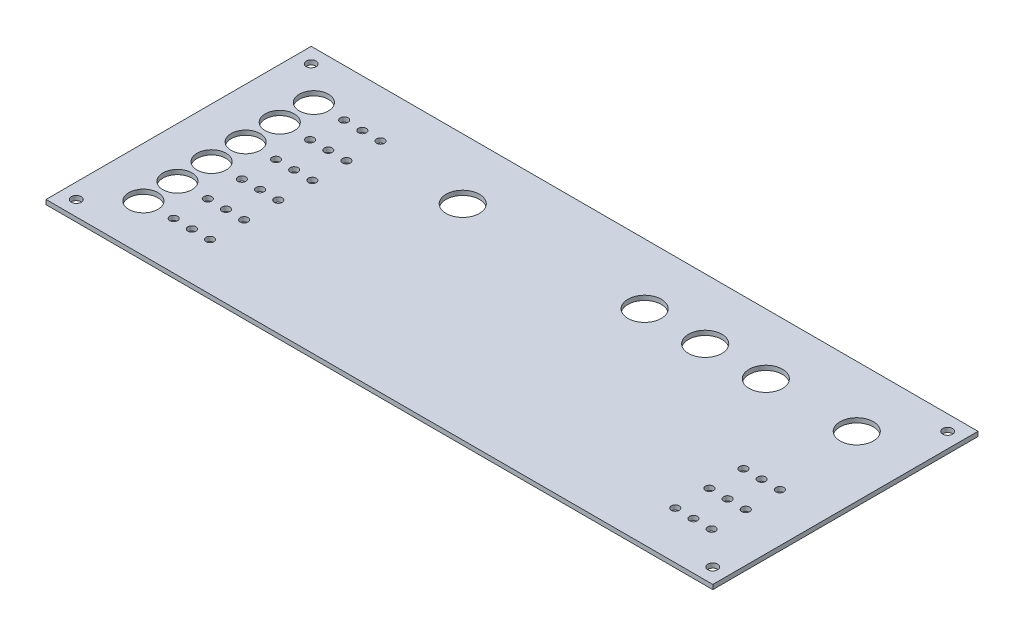
SolidWorks part; units mm, degrees
ref_plane "Front Plane" through (0, 0, 0) normal (0, 0, 1) x (1, 0, 0)
ref_plane "Top Plane" through (0, 0, 0) normal (0, 1, 0) x (1, 0, 0)
ref_plane "Right Plane" through (0, 0, 0) normal (1, 0, 0) x (0, 0, -1)
sketch "Sketch1" plane through (0, 0, 0) normal (0, 1, 0) x (1, 0, 0)
  line L0 (420, 20) -> (20, 20) construction
  line L1 (440, 175) -> (0, 175)
  line L2 (440, 175) -> (440, 0)
  line L3 (440, 0) -> (0, 0)
  line L4 (0, 175) -> (0, 0)
  line L5 (20, 155) -> (20, 20) construction
  line L6 (420, 155) -> (20, 155) construction
  line L7 (420, 155) -> (420, 20) construction
  line L9 (20, 143.75) -> (120, 143.75) construction
  line L10 (33, 20) -> (33, 155) construction
  line L11 (20, 121.25) -> (120, 121.25) construction
  line L12 (53, 20) -> (53, 155) construction
  line L13 (120, 98.75) -> (20, 98.75) construction
  line L14 (65, 20) -> (65, 155) construction
  line L15 (20, 76.25) -> (420, 76.25) construction
  line L16 (77, 20) -> (77, 155) construction
  line L17 (420, 53.75) -> (20, 53.75) construction
  line L19 (20, 31.25) -> (420, 31.25) construction
  line L20 (420, 135) -> (140, 135) construction
  circle A0 centre (10, 10) radius 3.25
  circle A1 centre (10, 165) radius 3.25
  circle A2 centre (430, 165) radius 3.25
  circle A3 centre (430, 10) radius 3.25
  circle A4 centre (33, 31.25) radius 9.6
  circle A5 centre (33, 53.75) radius 9.6
  circle A6 centre (33, 76.25) radius 9.6
  circle A7 centre (33, 98.75) radius 9.6
  circle A8 centre (33, 121.25) radius 9.6
  circle A9 centre (33, 143.75) radius 9.6
  circle A10 centre (33, 31.25) radius 11 construction
  circle A11 centre (33, 53.75) radius 11 construction
  circle A12 centre (53, 31.25) radius 2.6
  circle A13 centre (53, 53.75) radius 2.6
  circle A14 centre (53, 76.25) radius 2.6
  circle A15 centre (53, 98.75) radius 2.6
  circle A16 centre (53, 121.25) radius 2.6
  circle A17 centre (53, 143.75) radius 2.6
  circle A18 centre (65, 31.25) radius 2.6
  circle A19 centre (65, 53.75) radius 2.6
  circle A20 centre (65, 76.25) radius 2.6
  circle A21 centre (65, 98.75) radius 2.6
  circle A22 centre (65, 121.25) radius 2.6
  circle A23 centre (65, 143.75) radius 2.6
  circle A24 centre (77, 31.25) radius 2.6
  circle A25 centre (77, 53.75) radius 2.6
  circle A26 centre (77, 76.25) radius 2.6
  circle A27 centre (77, 98.75) radius 2.6
  circle A28 centre (77, 121.25) radius 2.6
  circle A29 centre (77, 143.75) radius 2.6
  circle A30 centre (400, 135) radius 11
  circle A31 centre (340, 135) radius 11
  circle A32 centre (300, 135) radius 11
  circle A33 centre (260, 135) radius 11
  circle A34 centre (140, 135) radius 11
  circle A35 centre (408, 31.25) radius 2.6
  circle A36 centre (396, 31.25) radius 2.6
  circle A37 centre (384, 31.25) radius 2.6
  circle A38 centre (408, 53.75) radius 2.6
  circle A39 centre (396, 53.75) radius 2.6
  circle A40 centre (384, 53.75) radius 2.6
  circle A41 centre (408, 76.25) radius 2.6
  circle A42 centre (396, 76.25) radius 2.6
  circle A43 centre (384, 76.25) radius 2.6
  point P104 (0, 0)
  point P117 (408.671, 53.75)
  point P118 (396.671, 53.75)
  point P119 (384.671, 53.75)
  point P120 (384, 76.25)
  point P121 (396, 76.25)
  point P122 (408, 76.25)
  point P123 (0, 0)
  point P124 (0, 0)
  dimension "D1" = 135
  dimension "D2" = 400
  dimension "D3" = 22.5
  dimension "D4" = 22.5
  dimension "D5" = 22.5
  dimension "D6" = 22.5
  dimension "D7" = 22.5
  dimension "D8" = 11.25
  dimension "D9" = 12
  dimension "D10" = 12
  dimension "D11" = 20
  dimension "D12" = 13
  dimension "D13" = 20
  dimension "D14" = 12
  dimension "D15" = 12
  dimension "D16" = 12
  dimension "D17" = 20
  dimension "D18" = 60
  dimension "D19" = 40
  dimension "D20" = 40
  dimension "D21" = 120
extrude "Boss-Extrude1" add sketch "Sketch1" along normal blind 3
